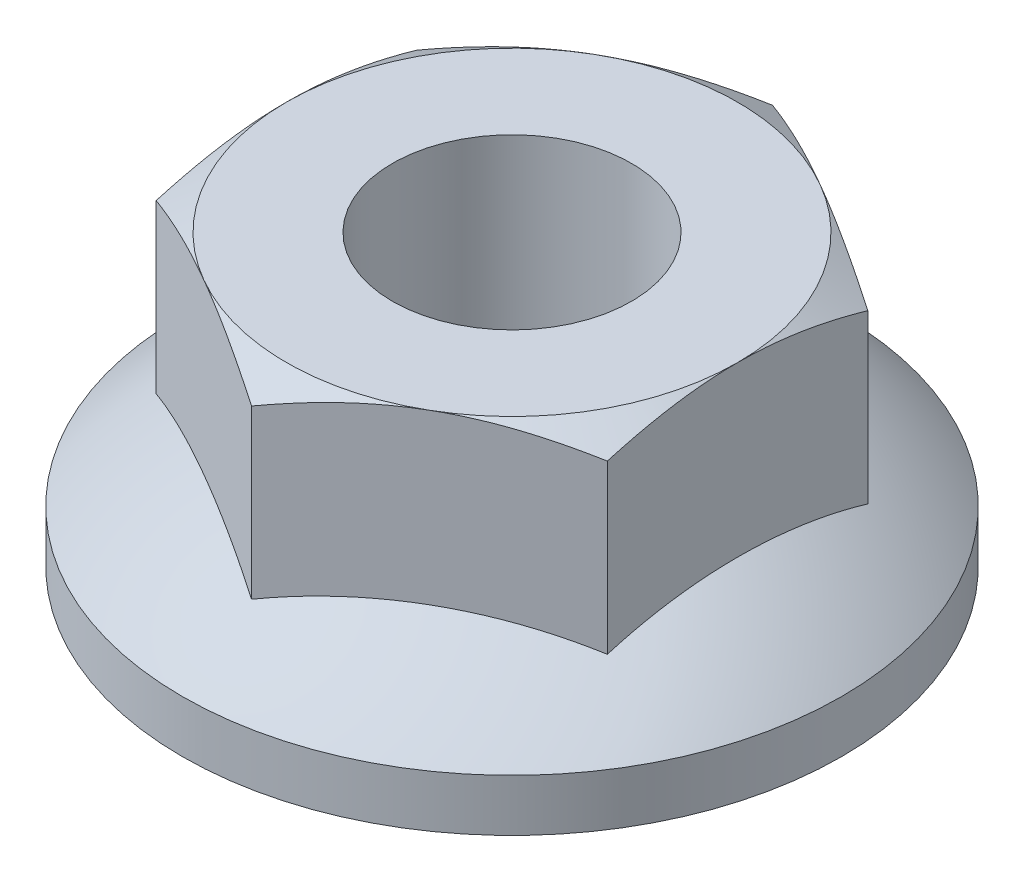
SolidWorks part; units mm, degrees
ref_plane "Front Plane" through (0, 0, 0) normal (0, 0, 1) x (1, 0, 0)
ref_plane "Top Plane" through (0, 0, 0) normal (0, 1, 0) x (1, 0, 0)
ref_plane "Right Plane" through (0, 0, 0) normal (1, 0, 0) x (0, 0, -1)
ref_axis "Axis_X" through (-88.99, 0, 0) along (1, 0, 0)
ref_axis "Axis_Y" through (0, 55, 0) along (0, -1, 0)
ref_axis "Axis_Z" through (0, 0, -88.99) along (0, 0, 1)
sketch "Sketch1" plane through (0, 0, 0) normal (0, 0, 1) x (1, 0, 0)
  line L0 (0, 0) -> (-5.7, 0)
  line L1 (0, 0) -> (0, 3) construction
  line L2 (-5.7, 0) -> (-5.7, 0.9)
  line L3 (0, 3) -> (0, 0)
  arc A0 (0, 3) -> (-5.7, 0.9) centre (0, -5.7857) ccw
  dimension "MSM_201" = 11.4
  dimension "MSM_202" = 0.9
  dimension "MSM_203" = 3
revolve "Revolve1" add sketch "Sketch1" angle 360 about axis through (0, 55, 0) along (0, -1, 0)
sketch "Sketch2" plane through (0, 0, 0) normal (0, -1, 0) x (1, 0, 0)
  line L0 (0, 4.5033) -> (0, 0) construction
  line L1 (0, 4.5033) -> (-3.9, 2.2517)
  line L2 (-3.9, 2.2517) -> (-3.9, -2.2517)
  line L3 (-3.9, -2.2517) -> (0, -4.5033)
  line L4 (0, -4.5033) -> (3.9, -2.2517)
  line L5 (3.9, -2.2517) -> (3.9, 2.2517)
  line L6 (3.9, 2.2517) -> (0, 4.5033)
  circle A0 centre (0, 0) radius 3.9 construction
  dimension "MSM_204" = 7.8
extrude "Boss-Extrude1" add sketch "Sketch2" against normal blind 5
sketch "Sketch3" plane through (0, 0, 0) normal (0, 0, 1) x (1, 0, 0)
  line L0 (-3.9, 5) -> (-5.9, 5)
  line L1 (0, 5) -> (-3.9, 5) construction
  line L2 (-5.9, 5) -> (-5.9, 3.8453)
  line L3 (-5.9, 3.8453) -> (-3.9, 5)
  line L4 (0, 0) -> (0, 5) construction
  dimension "MSM_204" = 7.8
  dimension "FIX_2" = 30
  dimension "FIX_3" = 2
revolve "Cut-Revolve1" cut sketch "Sketch3" angle 360 about axis through (0, 55, 0) along (0, -1, 0)
hole_wizard "Tap1" positions "Sketch5" profile "Sketch4" hole size "M5x0.8" standard "JIS" end condition through all
sketch "Sketch5" plane through (0, 5, 0) normal (0, 1, 0) x (1, 0, 0)
  point P0 (0, 0)
sketch "Sketch4" plane through (0, 5, 0) normal (1, 0, 0) x (0, 0, 1)
  line L0 (0, 0) -> (0, 5)
  line L1 (0, 5) -> (2.067, 5)
  line L2 (2.067, 5) -> (2.067, 0)
  line L5 (2.067, 0) -> (0, 0)
  line L11 (0, -6.35) -> (0, 107.95) construction
  dimension "HSD_201" = 4.134
  dimension "Thru Hole Depth" = 5
cosmetic thread "Thread1" parameters "MSM_206"=5
equation "\"Factor\"= 1.082532"
